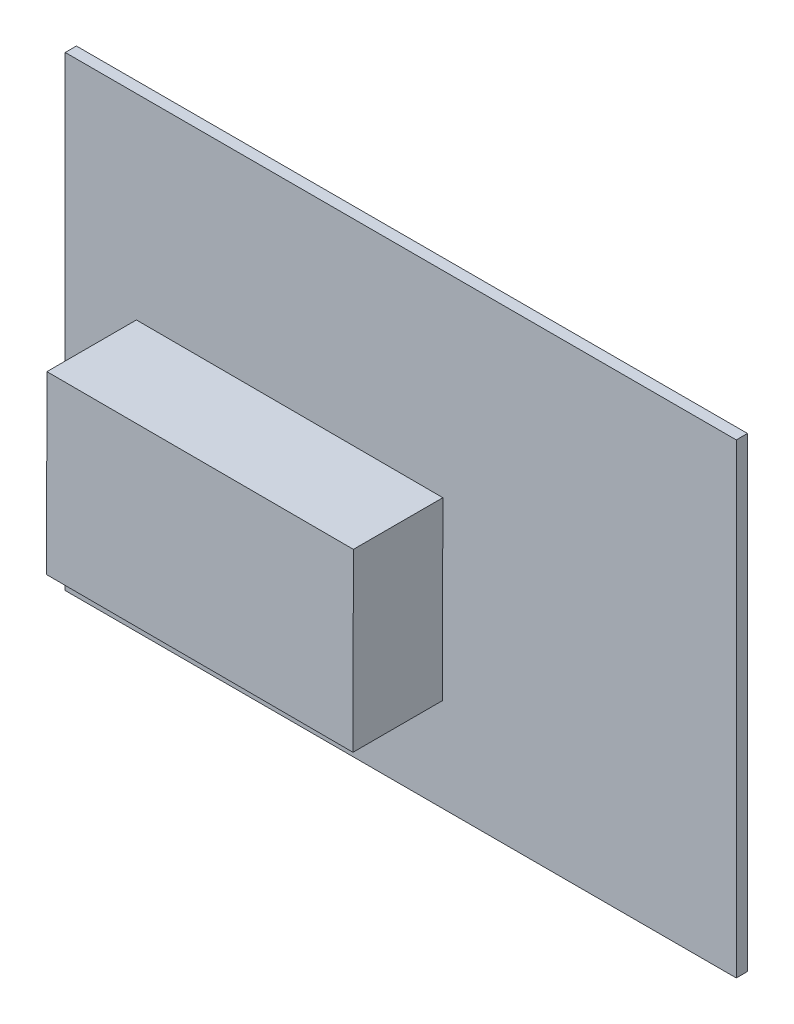
SolidWorks part; units mm, degrees
ref_plane "前视基准面" through (0, 0, 0) normal (0, 0, 1) x (1, 0, 0)
ref_plane "上视基准面" through (0, 0, 0) normal (0, 1, 0) x (1, 0, 0)
ref_plane "右视基准面" through (0, 0, 0) normal (1, 0, 0) x (0, 0, -1)
sketch "草图1" plane through (0, 0, 0) normal (0, 0, 1) x (1, 0, 0)
  line L1 (-90, 62.5) -> (90, 62.5)
  line L2 (-90, 62.5) -> (-90, -62.5)
  line L3 (-90, -62.5) -> (90, -62.5)
  line L4 (90, 62.5) -> (90, -62.5)
  line L5 (-90, 62.5) -> (90, -62.5) construction
  line L6 (-90, -62.5) -> (90, 62.5) construction
  point P0 (0, 0)
  dimension "D1" = 125
  dimension "D2" = 180
extrude "凸台-拉伸1" add sketch "草图1" along normal blind 3
sketch "草图2" plane through (0, 0, 3) normal (0, 0, 1) x (1, 0, 0)
  line L0 (8.1833, 6.6267) -> (8.0906, -34.3732) construction
  line L1 (-67.8165, 6.7986) -> (8.1833, 6.6267) construction
  line L2 (-67.9092, -34.2013) -> (-67.8165, 6.7986) construction
  line L3 (8.0906, -34.3732) -> (-67.9092, -34.2013) construction
  line L4 (8.1833, 6.6267) -> (8.0906, -34.3732) construction
  line L5 (-67.8165, 6.7986) -> (8.1833, 6.6267) construction
  line L6 (-67.9092, -34.2013) -> (-67.8165, 6.7986) construction
  line L7 (8.0906, -34.3732) -> (-67.9092, -34.2013) construction
  line L8 (8.2835, 6.7265) -> (8.1903, -34.4734)
  line L9 (8.1903, -34.4734) -> (-68.0095, -34.3011)
  line L10 (-68.0095, -34.3011) -> (-67.9163, 6.8988)
  line L11 (-67.9163, 6.8988) -> (8.2835, 6.7265)
  line L12 (11.1835, -37.4802) -> (-71.0163, -37.2943)
  line L13 (-71.0163, -37.2943) -> (-70.9095, 9.9056)
  line L14 (-70.9095, 9.9056) -> (11.2903, 9.7197)
  line L15 (11.2903, 9.7197) -> (11.1835, -37.4802)
  dimension "D1" = 0.1
  dimension "D2" = 3
extrude "凸台-拉伸2" add sketch "草图2" along normal offset from surface (24 mm away) 3 offset beyond the face yes
sketch "草图3" plane through (0, 0, 0) normal (0, 0, -1) x (-1, 0, 0)
  line L0 (67.9163, 6.8988) -> (68.0095, -34.3011) construction
  line L1 (67.9163, 6.8988) -> (68.0095, -34.3011)
  line L2 (68.0095, -34.3011) -> (-8.1903, -34.4734) construction
  line L3 (68.0095, -34.3011) -> (-8.1903, -34.4734)
  line L12 (-8.2835, 6.7265) -> (67.9163, 6.8988) construction
  line L13 (-8.2835, 6.7265) -> (67.9163, 6.8988)
  line L14 (-8.1903, -34.4734) -> (-8.2835, 6.7265) construction
  line L15 (-8.1903, -34.4734) -> (-8.2835, 6.7265)
extrude "切除-拉伸1" cut sketch "草图3" against normal up to next
extrude "凸台-拉伸3" add sketch "草图3<2>" along normal blind 3 from surface starting at face at (-29.863, -13.7873, 27)
sketch "草图3<2>" plane through (0, 0, 0) normal (0, 0, -1) x (-1, 0, 0) same geometry as "草图3"
sketch "草图4" plane through (0, 0, 0) normal (0, 0, -1) x (-1, 0, 0)
  line L14 (67.8957, -28.2013) -> (72.8957, -28.19) construction
  line L15 (72.8957, -28.19) -> (72.8844, -23.19) construction
  line L16 (72.8844, -23.19) -> (67.8844, -23.2013) construction
  line L17 (67.8414, -4.2014) -> (72.8414, -4.1901) construction
  line L18 (72.8414, -4.1901) -> (72.8301, 0.8099) construction
  line L19 (72.8301, 0.8099) -> (67.8301, 0.7986) construction
  line L20 (67.8957, -28.2013) -> (72.8957, -28.19) construction
  line L21 (72.8957, -28.19) -> (72.8844, -23.19) construction
  line L22 (72.8844, -23.19) -> (67.8844, -23.2013) construction
  line L23 (67.8414, -4.2014) -> (72.8414, -4.1901) construction
  line L24 (72.8414, -4.1901) -> (72.8301, 0.8099) construction
  line L25 (72.8301, 0.8099) -> (67.8301, 0.7986) construction
  line L26 (67.8959, -28.3013) -> (72.9959, -28.2898)
  line L27 (72.9959, -28.2898) -> (72.9841, -23.0898)
  line L28 (72.9841, -23.0898) -> (67.8841, -23.1013)
  line L29 (67.8416, -4.3014) -> (72.9416, -4.2898)
  line L30 (72.9416, -4.2898) -> (72.9298, 0.9101)
  line L31 (72.9298, 0.9101) -> (67.8299, 0.8986)
  line L32 (67.8299, 0.8986) -> (67.8416, -4.3014)
  line L33 (67.8841, -23.1013) -> (67.8959, -28.3013)
  dimension "D1" = 0.1
extrude "切除-拉伸2" cut sketch "草图4" against normal blind 1.6
chamfer "倒角1" distance 1 angle 45 1 edges at (-67.9629, -13.7011, 0)
